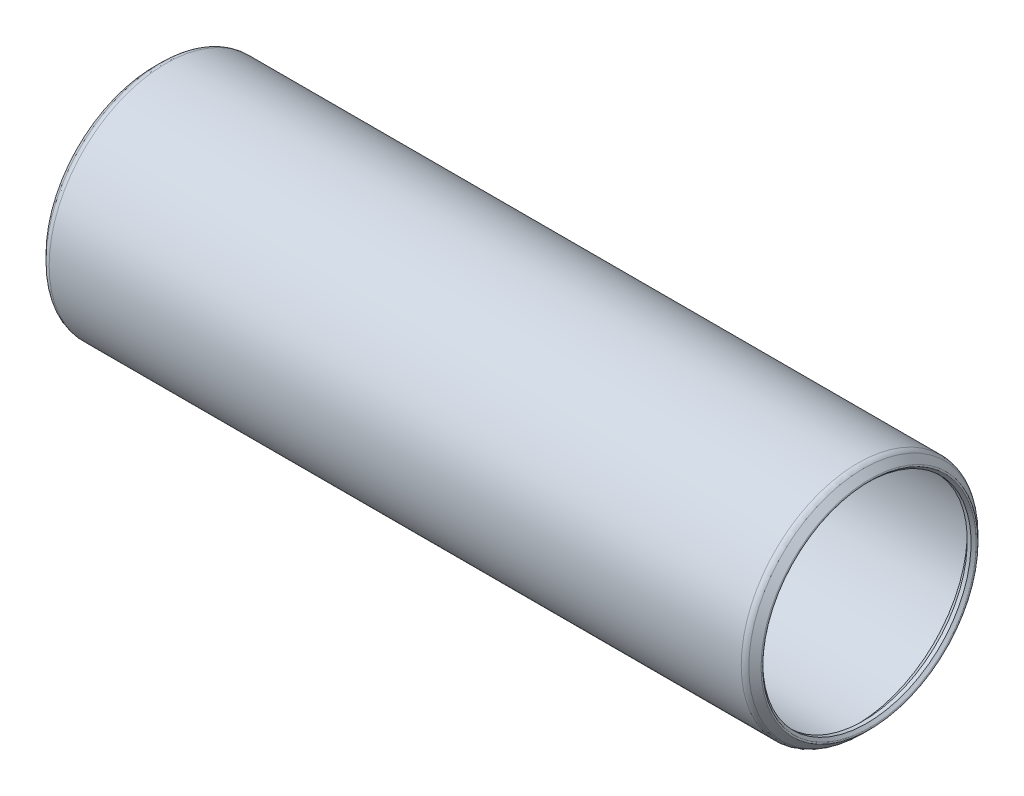
SolidWorks part; units mm, degrees
material "Cast Alloy Steel"
ref_plane "Front Plane" through (0, 0, 0) normal (0, 0, 1) x (1, 0, 0)
ref_plane "Top Plane" through (0, 0, 0) normal (0, 1, 0) x (1, 0, 0)
ref_plane "Right Plane" through (0, 0, 0) normal (1, 0, 0) x (0, 0, -1)
ref_plane "Plane1" through (70.7009, 0, 0) normal (1, 0, 0) x (0, 0, -1)
sketch "Sketch1" plane through (0, 0, 0) normal (0, 0, 1) x (1, 0, 0)
  line L0 (-0.6395, 10.7424) -> (-0.381, 10.4839)
  line L1 (-0.381, 10.4839) -> (0, 10.4839)
  line L2 (0, 10.4839) -> (0.762, 11.2459)
  line L3 (0.762, 11.2459) -> (69.9389, 11.2459)
  line L4 (69.9389, 11.2459) -> (70.7009, 10.4839)
  line L5 (70.7009, 10.4839) -> (71.0819, 10.4839)
  line L6 (71.0819, 10.4839) -> (71.3404, 10.7424)
  line L7 (71.3404, 10.922) -> (70.7254, 11.537)
  line L8 (70.1866, 11.7602) -> (0.5143, 11.7602)
  line L9 (-0.0245, 11.537) -> (-0.6395, 10.922)
  line L10 (70.7009, 0) -> (0, 0) construction
  arc A0 (-0.6395, 10.922) -> (-0.6395, 10.7424) centre (-0.5497, 10.8322) ccw
  arc A1 (71.3404, 10.7424) -> (71.3404, 10.922) centre (71.2506, 10.8322) ccw
  arc A2 (70.7254, 11.537) -> (70.1866, 11.7602) centre (70.1866, 10.9982) ccw
  arc A3 (0.5143, 11.7602) -> (-0.0245, 11.537) centre (0.5143, 10.9982) ccw
revolve "Revolve1" add sketch "Sketch1" angle 360 about L10 reverse direction yes
ref_plane "Plane2" through (35.3505, 0, 0) normal (1, 0, 0) x (0, 0, -1)
ref_plane "cp1 XY" through (35.3505, 0, 0) normal (1, 0, 0) x (0, 0, -1)
ref_plane "cp1 XZ" through (0, 11.7602, 0) normal (0, -1, 0) x (-1, 0, 0)
ref_plane "cp1 YZ" through (0, 0, 0) normal (0, 0, -1) x (-1, 0, 0)
ref_axis "cp1 X" through (35.3505, 11.7602, 80.9) along (0, 0, -1)
ref_axis "cp1 Y" through (35.3505, -50, 0) along (0, 1, 0)
ref_axis "cp1 Z" through (80.9, 11.7602, 0) along (-1, 0, 0)
sketch3d "cp1"
  point P0 (35.3505, 11.7602, 0)
ref_plane "cp2 XY" through (35.3505, 0, 0) normal (1, 0, 0) x (0, 0, -1)
ref_plane "cp2 XZ" through (0, 0, 0) normal (0, -1, 0) x (-1, 0, 0)
ref_plane "cp2 YZ" through (0, 0, -11.7602) normal (0, 0, -1) x (-1, 0, 0)
ref_axis "cp2 X" through (35.3505, 0, 80.9) along (0, 0, -1)
ref_axis "cp2 Y" through (35.3505, -50, -11.7602) along (0, 1, 0)
ref_axis "cp2 Z" through (80.9, 0, -11.7602) along (-1, 0, 0)
sketch3d "cp2"
  point P0 (35.3505, 0, -11.7602)
ref_plane "cp3 XY" through (35.3505, 0, 0) normal (1, 0, 0) x (0, 0, -1)
ref_plane "cp3 XZ" through (0, -11.7602, 0) normal (0, -1, 0) x (-1, 0, 0)
ref_plane "cp3 YZ" through (0, 0, 0) normal (0, 0, -1) x (-1, 0, 0)
ref_axis "cp3 X" through (35.3505, -11.7602, 80.9) along (0, 0, -1)
ref_axis "cp3 Y" through (35.3505, -50, 0) along (0, 1, 0)
ref_axis "cp3 Z" through (80.9, -11.7602, 0) along (-1, 0, 0)
sketch3d "cp3"
  point P0 (35.3505, -11.7602, 0)
ref_plane "cp4 XY" through (35.3505, 0, 0) normal (1, 0, 0) x (0, 0, -1)
ref_plane "cp4 XZ" through (0, 0, 0) normal (0, -1, 0) x (-1, 0, 0)
ref_plane "cp4 YZ" through (0, 0, 11.7602) normal (0, 0, -1) x (-1, 0, 0)
ref_axis "cp4 X" through (35.3505, 0, 80.9) along (0, 0, -1)
ref_axis "cp4 Y" through (35.3505, -50, 11.7602) along (0, 1, 0)
ref_axis "cp4 Z" through (80.9, 0, 11.7602) along (-1, 0, 0)
sketch3d "cp4"
  point P0 (35.3505, 0, 11.7602)
ref_plane "tube_front XY" through (0, 0, 0) normal (1, 0, 0) x (0, 0, -1)
ref_plane "tube_front XZ" through (0, 0, 0) normal (0, -1, 0) x (-1, 0, 0)
ref_plane "tube_front YZ" through (0, 0, 0) normal (0, 0, -1) x (-1, 0, 0)
ref_axis "tube_front X" through (0, 0, 80.9) along (0, 0, -1)
ref_axis "tube_front Y" through (0, -50, 0) along (0, 1, 0)
ref_axis "tube_front Z" through (80.9, 0, 0) along (-1, 0, 0)
sketch3d "tube_front"
  point P0 (0, 0, 0)
ref_plane "tube_rear XY" through (70.7009, 0, 0) normal (1, 0, 0) x (0, 0, -1)
ref_plane "tube_rear XZ" through (0, 0, 0) normal (0, -1, 0) x (-1, 0, 0)
ref_plane "tube_rear YZ" through (0, 0, 0) normal (0, 0, -1) x (-1, 0, 0)
ref_axis "tube_rear X" through (70.7009, 0, 80.9) along (0, 0, -1)
ref_axis "tube_rear Y" through (70.7009, -50, 0) along (0, 1, 0)
ref_axis "tube_rear Z" through (80.9, 0, 0) along (-1, 0, 0)
sketch3d "tube_rear"
  point P0 (70.7009, 0, 0)
